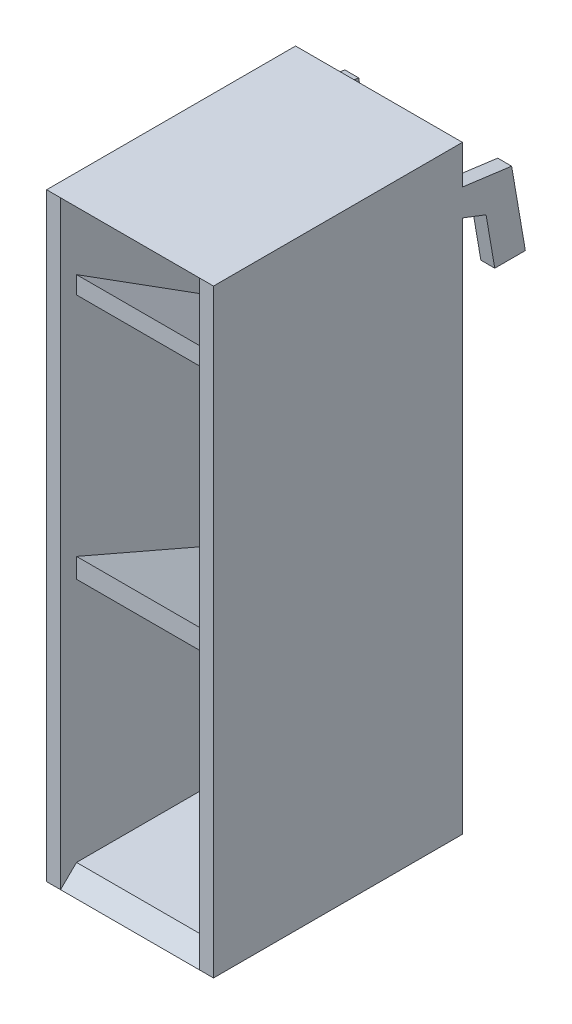
SolidWorks part; units mm, degrees
ref_plane "Front Plane" through (0, 0, 0) normal (0, 0, 1) x (1, 0, 0)
ref_plane "Top Plane" through (0, 0, 0) normal (0, 1, 0) x (1, 0, 0)
ref_plane "Right Plane" through (0, 0, 0) normal (1, 0, 0) x (0, 0, -1)
sketch "Sketch1" plane through (0, 0, 0) normal (1, 0, 0) x (0, 0, -1)
  line L0 (-35.7578, 29.6147) -> (-3.7744, 9.358)
  line L1 (-35.7578, 39.0356) -> (-3.7744, 39.0356)
  line L3 (-35.7578, -43.6046) -> (-3.7744, -43.6046)
  line L4 (-3.7744, 39.0356) -> (-3.7744, -43.6046)
  line L5 (-35.7578, -5.4865) -> (-3.7744, -19.326)
  line L6 (-3.7744, -21.6749) -> (-35.7578, -8.335)
  line L7 (-2.2553, 34.7722) -> (4.8244, 33.8338)
  line L8 (4.8244, 33.8338) -> (6.7983, 22.3319)
  line L9 (6.7983, 22.3319) -> (2.3965, 22.3319)
  line L10 (2.3965, 22.3319) -> (1.1467, 29.6147)
  line L11 (-3.7744, 7.7922) -> (-35.7578, 27.0808)
  line L12 (-2.2553, 40.3412) -> (-38.0606, 40.3412)
  line L13 (-2.2553, 40.3412) -> (-2.2553, -45.8519)
  line L14 (-2.2553, -45.8519) -> (-38.0606, -45.8519)
  line L16 (1.1467, 29.6147) -> (-2.2553, 30.9243)
  line L17 (-35.7578, 39.0356) -> (-38.0606, 40.3412)
  line L18 (-38.0606, 40.3412) -> (-38.0606, -45.8519)
  line L19 (-38.0606, -45.8519) -> (-35.7578, -43.6046)
  line L20 (-35.7578, 27.0808) -> (-35.7578, 29.6147)
  line L21 (-35.7578, -8.335) -> (-35.7578, -5.4865)
extrude "Boss-Extrude1" add sketch "Sketch1" along normal blind 10 contours L12 L14 L13 L1 L4 L3 | L11 L4 L0 | L6 L4 L5 region at (0, 19.2396, 21.0248) region at (0, 24.1968, 2.8411) region at (0, -13.4879, 20.2785)
extrude "Boss-Extrude2" add sketch "Sketch1<4>" against normal blind 2 contours L21 L6 L4 L5 | L20 L11 L4 L0 | L19 L14 L13 L12 L17 L1 L4 L3 | L16 L10 L9 L8 L7 L13 | L6 L21 L5 L4 L11 L20 L0 L1 L17 L18 L19 L3 region at (0, -2.4802, 20.9596) region at (0, 19.2396, 21.0248) region at (0, 24.1968, 2.8411) region at (0, -13.4879, 20.2785) region at (0, 29.0339, -2.7313)
sketch "Sketch1<4>" plane through (0, 0, 0) normal (1, 0, 0) x (0, 0, -1) same geometry as "Sketch1"
mirror "Mirror1" about plane through (10, 0, 0) normal (1, 0, 0) of "Boss-Extrude1", "Boss-Extrude2"
